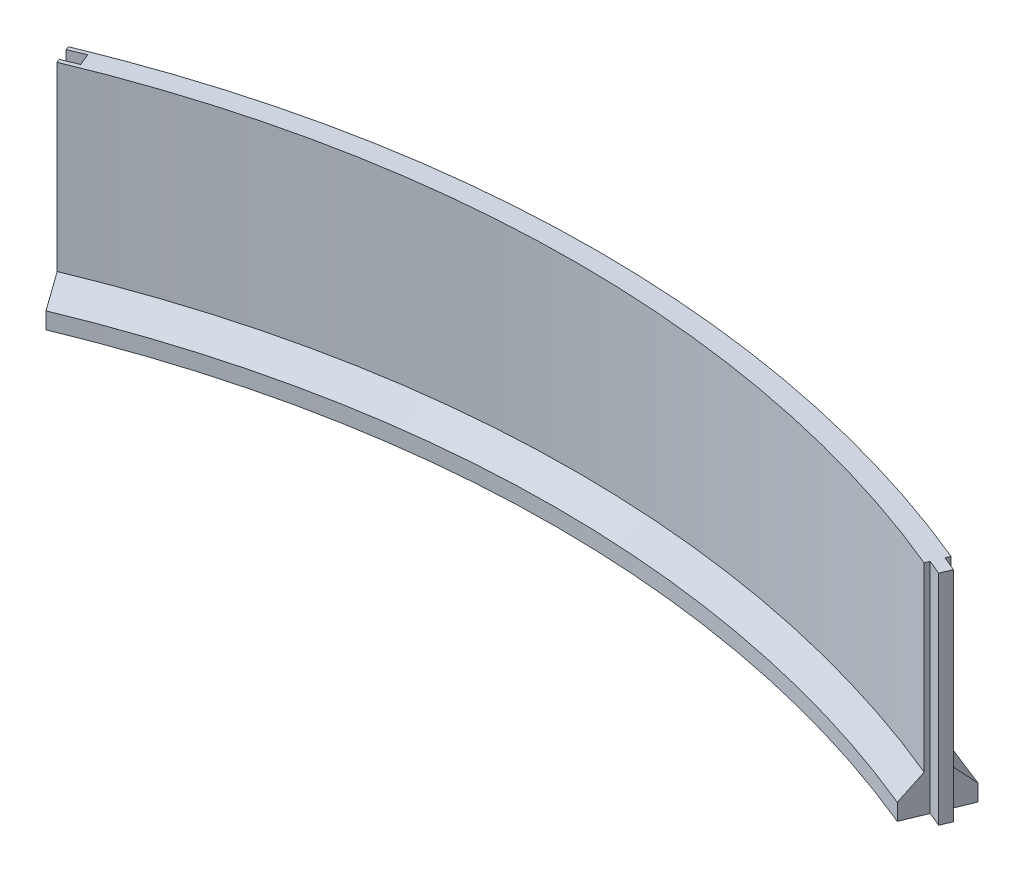
SolidWorks part; units mm, degrees
ref_plane "Front Plane" through (0, 0, 0) normal (0, 0, 1) x (1, 0, 0)
ref_plane "Top Plane" through (0, 0, 0) normal (0, 1, 0) x (1, 0, 0)
ref_plane "Right Plane" through (0, 0, 0) normal (1, 0, 0) x (0, 0, -1)
sketch "Sketch2" plane through (0, 0, 0) normal (0, 1, 0) x (1, 0, 0)
  line L0 (0, 0) -> (0, 184.9275) construction
  line L1 (-52.619, 127.0334) -> (-52.7956, 127.4598)
  line L2 (52.619, 127.0334) -> (53.5757, 129.3431) construction
  line L3 (0, 0) -> (-52.619, 127.0334) construction
  line L4 (0, 0) -> (52.619, 127.0334) construction
  line L5 (-52.619, 127.0334) -> (-52.7956, 127.4598) construction
  line L6 (-53.0973, 128.1883) -> (-50.3257, 129.3363) construction
  line L7 (-53.3991, 128.9168) -> (-51.5513, 129.6821)
  line L8 (-51.5513, 129.6821) -> (-50.9478, 128.2252)
  line L9 (-50.9478, 128.2252) -> (-52.7956, 127.4598)
  line L10 (-52.7956, 127.4598) -> (-53.0973, 128.1883) construction
  line L11 (-53.3991, 128.9168) -> (-53.5757, 129.3431)
  line L12 (-52.7956, 127.4598) -> (-53.0973, 128.1883) construction
  line L13 (-53.3991, 128.9168) -> (-53.5757, 129.3431) construction
  line L14 (-53.0973, 128.1883) -> (-53.3991, 128.9168) construction
  line L15 (-53.0973, 128.1883) -> (-53.3991, 128.9168) construction
  line L16 (50.9478, 128.2252) -> (54.6433, 126.6944) construction
  line L17 (51.5513, 129.6821) -> (50.9478, 128.2252) construction
  line L18 (55.2468, 128.1514) -> (51.5513, 129.6821) construction
  line L19 (55.2468, 128.1514) -> (54.6433, 126.6944) construction
  line L20 (53.3991, 128.9168) -> (55.2468, 128.1514) construction
  line L21 (54.6433, 126.6944) -> (52.7956, 127.4598) construction
  line L22 (52.7956, 127.4598) -> (52.619, 127.0334)
  line L23 (53.5757, 129.3431) -> (53.3991, 128.9168)
  line L24 (53.3608, 128.8244) -> (55.1162, 128.0973)
  line L25 (55.1162, 128.0973) -> (54.5892, 126.8251)
  line L26 (54.5892, 126.8251) -> (52.8338, 127.5522)
  line L27 (53.3991, 128.9168) -> (53.3608, 128.8244)
  line L28 (52.8338, 127.5522) -> (52.7956, 127.4598)
  arc A0 (53.5757, 129.3431) -> (-53.5757, 129.3431) centre (0, 0) ccw
  arc A1 (52.619, 127.0334) -> (-52.619, 127.0334) centre (0, 0) ccw
  arc A2 (-52.619, 127.0334) -> (52.619, 127.0334) centre (0, 0) ccw construction
  arc A3 (-53.5757, 129.3431) -> (53.5757, 129.3431) centre (0, 0) ccw construction
  point P18 (52.7956, 127.4598)
  point P19 (53.3991, 128.9168)
  dimension "D1" = 280
  dimension "D2" = 275
  dimension "D3" = 45
  dimension "D4" = 3
  dimension "D5" = 1.577
  dimension "D6" = 2
  dimension "D7" = 1.25
  dimension "D8" = 0.1
extrude "Boss-Extrude1" add sketch "Sketch2" along normal mid plane 26.5
sketch "Sketch3" plane through (0, -13.25, 0) normal (0, -1, 0) x (1, 0, 0)
  line L0 (-52.7956, -127.4598) -> (-53.3991, -128.9168) construction
  line L1 (-53.3991, -128.9168) -> (-54.5324, -131.6528)
  line L2 (-52.7956, -127.4598) -> (-50.9478, -128.2252)
  line L3 (-52.619, -127.0334) -> (-52.7956, -127.4598)
  line L5 (-51.6623, -124.7237) -> (-52.7956, -127.4598)
  line L6 (51.6623, -124.7237) -> (52.619, -127.0334)
  line L7 (53.5757, -129.3431) -> (54.5324, -131.6528)
  line L14 (-52.7956, -127.4598) -> (-50.9478, -128.2252)
  line L15 (-50.9478, -128.2252) -> (-51.5513, -129.6821)
  line L16 (-50.9478, -128.2252) -> (-51.5513, -129.6821)
  line L17 (-51.5513, -129.6821) -> (-53.3991, -128.9168)
  line L18 (-51.5513, -129.6821) -> (-53.3991, -128.9168)
  line L19 (-53.3991, -128.9168) -> (-53.5757, -129.3431)
  line L20 (-53.3991, -128.9168) -> (-53.5757, -129.3431)
  line L21 (53.5757, -129.3431) -> (53.3608, -128.8244)
  line L22 (53.5757, -129.3431) -> (53.3608, -128.8244)
  line L23 (53.3608, -128.8244) -> (55.1162, -128.0973)
  line L24 (53.3608, -128.8244) -> (55.1162, -128.0973)
  line L25 (55.1162, -128.0973) -> (54.5892, -126.8251)
  line L26 (55.1162, -128.0973) -> (54.5892, -126.8251)
  line L27 (54.5892, -126.8251) -> (52.8338, -127.5522)
  line L28 (54.5892, -126.8251) -> (52.8338, -127.5522)
  line L29 (52.8338, -127.5522) -> (52.619, -127.0334)
  line L30 (52.8338, -127.5522) -> (52.619, -127.0334)
  arc A0 (-54.5324, -131.6528) -> (54.5324, -131.6528) centre (0, 0) ccw
  arc A1 (-53.5757, -129.3431) -> (53.5757, -129.3431) centre (0, 0) ccw construction
  arc A2 (-52.619, -127.0334) -> (52.619, -127.0334) centre (0, 0) ccw
  arc A3 (-53.5757, -129.3431) -> (53.5757, -129.3431) centre (0, 0) ccw
  arc A4 (-52.619, -127.0334) -> (52.619, -127.0334) centre (0, 0) ccw construction
  arc A5 (-53.5757, -129.3431) -> (53.5757, -129.3431) centre (0, 0) ccw
  arc A6 (-52.619, -127.0334) -> (52.619, -127.0334) centre (0, 0) ccw construction
  arc A7 (-51.6623, -124.7237) -> (51.6623, -124.7237) centre (0, 0) ccw
  dimension "D1" = 0
  dimension "D2" = 2.5
  dimension "D3" = 2.5
extrude "Boss-Extrude2" add sketch "Sketch3" against normal blind 2
chamfer "Chamfer2" distance 2.5 angle 45 2 edges at (0, -11.25, -137.5) (0, -11.25, -140)
